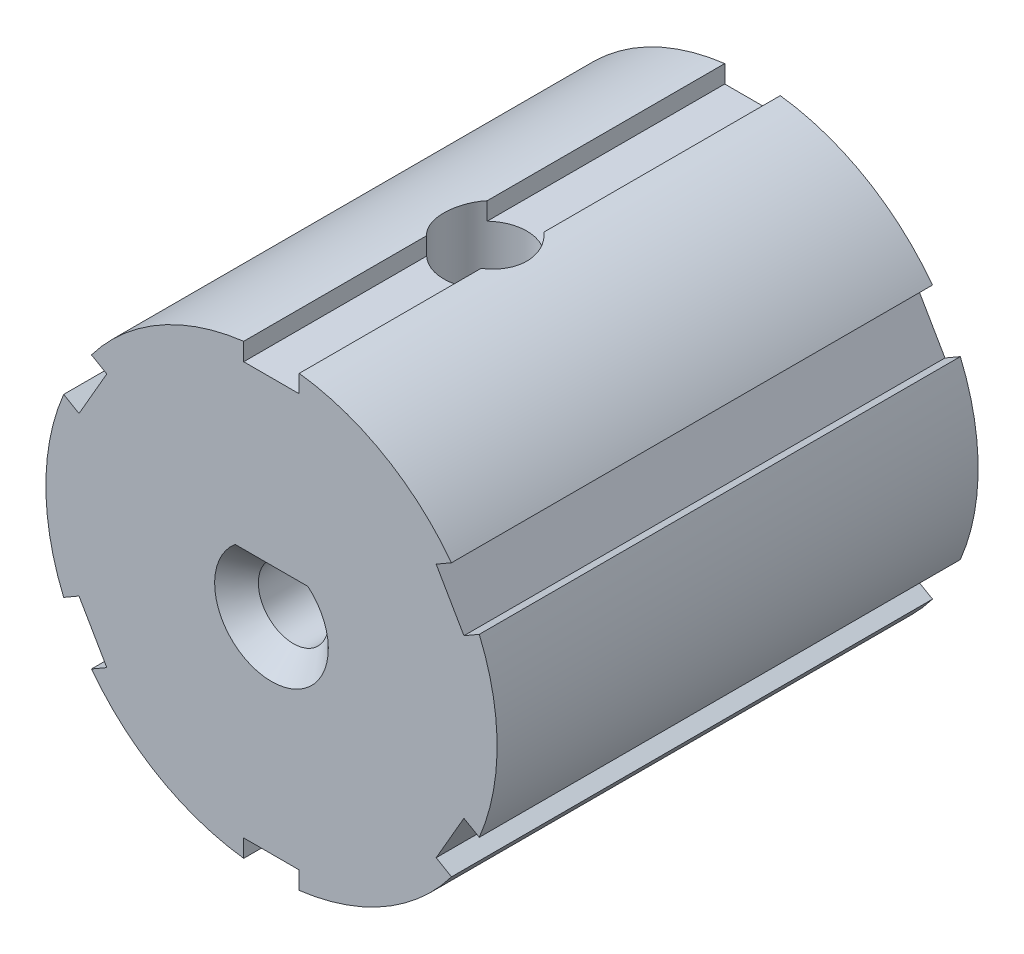
SolidWorks part; units mm, degrees
ref_plane "Спереди" through (0, 0, 0) normal (0, 0, 1) x (1, 0, 0)
ref_plane "Сверху" through (0, 0, 0) normal (0, 1, 0) x (1, 0, 0)
ref_plane "Справа" through (0, 0, 0) normal (1, 0, 0) x (0, 0, -1)
sketch "Эскиз1" plane through (0, 0, 0) normal (0, 0, 1) x (1, 0, 0)
  line L19 (13.2013, -7.8554) -> (13.9033, -8.2607)
  line L20 (13.9033, -0.2201) -> (13.2013, -0.6254)
  line L21 (13.2013, -0.6254) -> (11.9313, 1.5743)
  line L22 (11.9313, 1.5743) -> (12.6333, 1.9796)
  line L23 (5.6699, 5.9999) -> (5.6699, 5.1893)
  line L24 (5.6699, 5.1893) -> (3.1299, 5.1893)
  line L25 (3.1299, 5.1893) -> (3.1299, 5.9999)
  line L26 (-3.8335, 1.9796) -> (-3.1315, 1.5743)
  line L27 (-3.1315, 1.5743) -> (-4.4015, -0.6254)
  line L28 (-4.4015, -0.6254) -> (-5.1035, -0.2201)
  line L29 (-5.1035, -8.2607) -> (-4.4015, -7.8554)
  line L30 (-4.4015, -7.8554) -> (-3.1315, -10.0551)
  line L31 (-3.1315, -10.0551) -> (-3.8335, -10.4604)
  line L32 (3.1299, -14.4807) -> (3.1299, -13.6702)
  line L33 (3.1299, -13.6702) -> (5.6699, -13.6702)
  line L34 (5.6699, -13.6702) -> (5.6699, -14.4807)
  line L35 (12.6333, -10.4604) -> (11.9313, -10.0551)
  line L36 (11.9313, -10.0551) -> (13.2013, -7.8554)
  line L37 (3.1509, -3.2404) -> (5.6489, -3.2404)
  arc A7 (13.9033, -8.2607) -> (13.9033, -0.2201) centre (4.3999, -4.2404) ccw
  arc A8 (12.6333, 1.9796) -> (5.6699, 5.9999) centre (4.3999, -4.2404) ccw
  arc A9 (3.1299, 5.9999) -> (-3.8335, 1.9796) centre (4.3999, -4.2404) ccw
  arc A10 (-5.1035, -0.2201) -> (-5.1035, -8.2607) centre (4.3999, -4.2404) ccw
  arc A11 (-3.8335, -10.4604) -> (3.1299, -14.4807) centre (4.3999, -4.2404) ccw
  arc A12 (5.6699, -14.4807) -> (12.6333, -10.4604) centre (4.3999, -4.2404) ccw
  arc A16 (3.1509, -3.2404) -> (5.6489, -3.2404) centre (4.3999, -4.2404) ccw
  point P31 (4.3999, -2.7404)
  dimension "D1" = 0.5
  dimension "D2" = 3.2
extrude "Бобышка-Вытянуть1" add sketch "Эскиз1" along normal blind 22
sketch "Эскиз2" plane through (0, 0, 0) normal (0, 0, -1) x (-1, 0, 0)
  circle A4 centre (-4.3999, -4.2404) radius 8.75
  dimension "D1" = 17.5
extrude "Вырез-Вытянуть1" cut sketch "Эскиз2" against normal blind 9
sketch "Эскиз4" plane through (0, 5.1893, 0) normal (0, 1, 0) x (1, 0, 0)
  line L0 (3.1299, -15.4991) -> (5.6699, -15.4991) construction
  line L1 (4.4287, -15.4991) -> (4.4287, -8.9983) construction
  line L4 (3.1299, -22) -> (3.1299, 0) construction
  line L6 (5.6699, -22) -> (5.6699, 0) construction
  circle A0 centre (4.4287, -12.2487) radius 1.9
  point P0 (4.4287, -15.4991)
  dimension "D1" = 3.8
extrude "Вырез-Вытянуть3" cut sketch "Эскиз4" against normal up to surface (8.4298 mm away) and the other way blind 1 contours A0 up to face at (4.3999, -3.2404, 15.5)
chamfer "Фаска2" distance 1 angle 45 4 edges at (4.3999, -5.8404, 22) (4.3999, -3.2404, 22) (4.3999, -5.8404, 9) (4.3999, -3.2404, 9)
